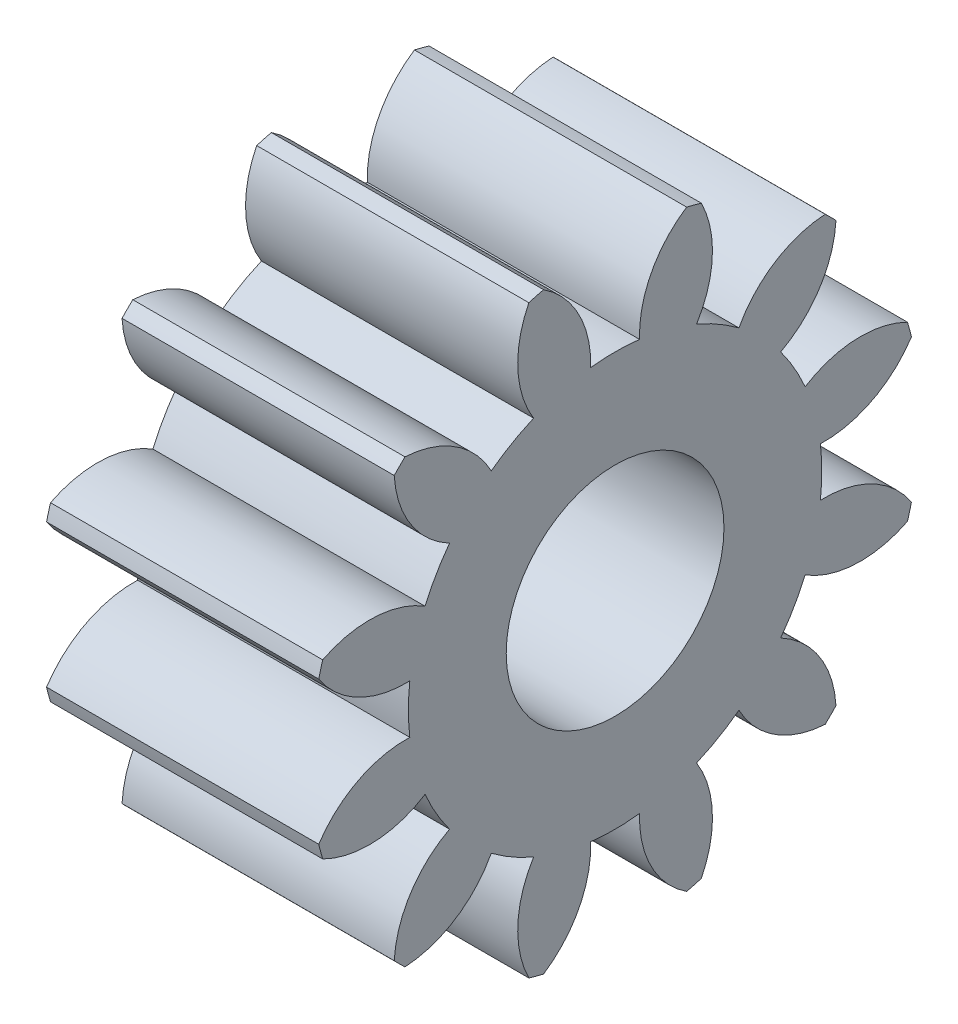
SolidWorks part; units mm, degrees
ref_plane "Plane1" through (0, 0, 0) normal (0, 0, 1) x (1, 0, 0)
ref_plane "Plane2" through (0, 0, 0) normal (0, 1, 0) x (1, 0, 0)
ref_plane "Plane3" through (0, 0, 0) normal (1, 0, 0) x (0, 0, -1)
sketch "HoldingSke" plane through (0, 0, 0) normal (0, 1, 0) x (1, 0, 0)
  line L0 (0, 0) -> (2.4454, -0.5198)
  line L1 (-15, 0) -> (100, 0) construction
  line L2 (0, 0) -> (-2.1039, 2.3779)
  line L3 (0, 0) -> (-11.863, 4.5341)
  line L4 (0, 0) -> (8.4473, 1.7955)
  line L5 (0, 0) -> (-46.8476, -17.4728)
  line L6 (0, 0) -> (-2.0724, -1.3983)
  line L7 (-2.1039, 2.3779) -> (8.6586, 51.2059)
  line L8 (-76.2, 54.61) -> (-75.9, 54.61)
  line L9 (-71.009, 38.7566) -> (-53.1078, 45.2721)
  line L10 (-76.2, 71.12) -> (104.1128, 71.12)
  line L11 (0, 0) -> (-2.5, 0)
  line L12 (-76.2, 101.6) -> (-76.185, 101.6)
  line L13 (24.9733, 27.94) -> (52.9518, 28.4284)
  line L14 (24.9733, 27.94) -> (24.9743, 27.94)
  line L15 (24.9733, 27.94) -> (100.4006, 29.5858)
  line L16 (-63.627, -0.4) -> (-12.827, -0.4)
  circle A0 centre (0, 0) radius 1
  circle A1 centre (0, 0) radius 1.899
  circle A2 centre (0, 0) radius 37.5
  circle A3 centre (0, 0) radius 1
  dimension "Num_teeth" = 12
  dimension "Pitch_radius" = 180.3128
  dimension "Width" = 2.5
  dimension "Thickness" = 2.5
sketch "BasProSke" plane through (0, 0, 0) normal (0, 1, 0) x (1, 0, 0)
  line L0 (-10, 0) -> (60, 0) construction
  line L1 (0, 0) -> (0, 2.8)
  line L2 (0, 0) -> (2.5, 0)
  line L3 (2.5, 0) -> (2.5, 2.8)
  line L4 (2.5, 2.8) -> (0, 2.8)
  dimension "Thickness" = 2.5
  dimension "Diameter" = 5.6
revolve "Base-Revolve" add sketch "BasProSke" angle 360 about L0
sketch "TooCutSke" plane through (0, 0, 0) normal (1, 0, 0) x (0, 0, -1)
  line L1 (0, 0) -> (0, 107) construction
  line L2 (0, 0) -> (-0.3395, 2.3759) construction
  line L3 (0, 0) -> (-1.2334, 4.6032) construction
  line L4 (-0.3395, 2.3759) -> (-0.6167, 2.3016) construction
  arc A0 (0.2246, 1.8857) -> (-0.2246, 1.8857) centre (0, 0) ccw
  arc A1 (0.6868, 2.7407) -> (-0.6868, 2.7407) centre (0, 0) ccw
  circle A2 centre (0, 0) radius 2.4 construction
  circle A3 centre (0, 0) radius 2.2553 construction
  arc A4 (-0.2246, 1.8857) -> (-0.6868, 2.7407) centre (-1.184, 1.9194) ccw
  arc A5 (0.6868, 2.7407) -> (0.2246, 1.8857) centre (1.184, 1.9194) ccw
extrude "ToothCut" cut sketch "TooCutSke" along normal through all
fillet "Breaks" [suppressed] radius 0.008 tangent propagation no
fillet "RootFillets" [suppressed] radius 0.101
pattern_circular "TeethCuts" count 12 every 30 about axis through (-10, 0, 0) along (1, 0, 0) of "ToothCut", "RootFillets", "Breaks"
sketch "HubNeaOneSke" plane through (0, 0, 0) normal (-1, 0, 0) x (0, 0, 1)
  circle A0 centre (0, 0) radius 1.899
  dimension "Diameter" = 3.798
extrude "HubNearOne" [suppressed] add sketch "HubNeaOneSke" along normal blind 47.5001
sketch "HubNeaBotSke" plane through (0, 0, 0) normal (-1, 0, 0) x (0, 0, 1)
  circle A0 centre (0, 0) radius 1.899
  dimension "Diameter" = 3.798
extrude "HubNearBoth" [suppressed] add sketch "HubNeaBotSke" along normal blind 23.75
ref_plane "FarPln" through (2.5, 0, 0) normal (1, 0, 0) x (0, 0, -1)
sketch "HubFarSke" plane through (2.5, 0, 0) normal (1, 0, 0) x (0, 0, -1)
  circle A0 centre (0, 0) radius 1.899
  dimension "Diameter" = 3.798
extrude "HubFar" [suppressed] add sketch "HubFarSke" along normal blind 23.75
sketch "BorSke" plane through (0, 0, 0) normal (1, 0, 0) x (0, 0, -1)
  circle A0 centre (0, 0) radius 1
  dimension "Diameter" = 2
extrude "Bore" cut sketch "BorSke" along normal mid plane 100.0001
sketch "KeySke" plane through (0, 0, 0) normal (1, 0, 0) x (0, 0, -1)
  line L0 (-0.4, 0) -> (-0.4, 1.3)
  line L1 (-0.4, 1.3) -> (0.4, 1.3)
  line L2 (0.4, 1.3) -> (0.4, 0)
  line L3 (0, 0) -> (0, 34) construction
  line L4 (-0.4, 0) -> (0.4, 0)
  dimension "Width" = 0.8
extrude "Keyway" [suppressed] cut sketch "KeySke" along normal mid plane 100.0001
pattern_circular "Keyway2" [suppressed] count 2 every 90 about axis through (-10, 0, 0) along (1, 0, 0) reverse direction yes
equation "' \"Module@HoldingSke\" = 6.35"
equation "' \"Num_teeth@HoldingSke\" = 12"
equation "' \"Ap@HoldingSke\" =  20"
equation "' \"Ap@HoldingSke\" = 20"
equation "' \"Width@HoldingSke\" = 0.5 * 25.4"
equation "' \"Hub_dia@HoldingSke\"= 1 * 25.4"
equation "' \"Hub_dia@HoldingSke\" = 1 * 25.4"
equation "' \"Overall_len@HoldingSke\" = 1.0 * 25.4"
equation "' \"Bore@HoldingSke\" = 0.75 * 25.4"
equation "' \"T_dim@HoldingSke\" = 0.1 * 25.4"
equation "' \"Width@KeySke\" = 0.25 * 25.4"
equation "' \"Show_teeth@HoldingSke\" = 13"
equation "' \"Backlash@HoldingSke\" = 0.009 * 25.4"
equation "' \"Addendum_fac@HoldingSke\" = 1.0"
equation "' \"Dedendum_fac@HoldingSke\" = 1.25"
equation "' \"Dedendum_add@HoldingSke\" = 0.00005 * 25.4"
equation "' \"Clearance_fac@HoldingSke\" = 0.25"
equation "\"Pitch@HoldingSke\" = 1 / \"Module@HoldingSke\""
equation "\"Overcut_dia@TooCutSke\" = (\"Num_teeth@HoldingSke\" + 2 * \"Addendum_fac@HoldingSke\") / \"Pitch@HoldingSke\" + 0.002 * 25.4"
equation "\"Pitch_dia@TooCutSke\" = \"Num_teeth@HoldingSke\" / \"Pitch@HoldingSke\""
equation "\"Base_dia@TooCutSke\" = \"Num_teeth@HoldingSke\" / \"Pitch@HoldingSke\" * cos((\"Ap@HoldingSke\"  * 3.14159265 / 180))"
equation "\"Root_dia@TooCutSke\" = (\"Num_teeth@HoldingSke\" + 2) / \"Pitch@HoldingSke\" - 2 * (\"Addendum_fac@HoldingSke\" + \"Dedendum_fac@HoldingSke\") / \"Pitch@HoldingSke\" - \"Dedendum_add@HoldingSke\" * 2"
equation "\"Half_ang@TooCutSke\" = 180 / \"Num_teeth@HoldingSke\""
equation "\"Half_CT@TooCutSke\" = \"Num_teeth@HoldingSke\" / \"Pitch@HoldingSke\" * sin((3.14159265 / 2 / \"Num_teeth@HoldingSke\")) / 2 - 7 * \"Backlash@HoldingSke\" / 4"
equation "\"Flank_rad@TooCutSke\" = \"Num_teeth@HoldingSke\" / \"Pitch@HoldingSke\" / 5"
equation "\"Radius@RootFillets\" = \"Clearance_fac@HoldingSke\" / \"Pitch@HoldingSke\" + \"Dedendum_add@HoldingSke\""
equation "\"Break_rad@Breaks\" = 0.02 / \"Pitch@HoldingSke\""
equation "\"Thickness@HoldingSke\" = \"Width@HoldingSke\""
equation "\"OAL@HoldingSke\" = \"Thickness@HoldingSke\""
equation "\"MHD@HoldingSke\" = (\"Num_teeth@HoldingSke\" + 2) / \"Pitch@HoldingSke\" - 2 * (\"Addendum_fac@HoldingSke\" + \"Dedendum_fac@HoldingSke\")  / \"Pitch@HoldingSke\" - \"Dedendum_add@HoldingSke\" * 2"
equation "\"MBD@HoldingSke\" = (\"Num_teeth@HoldingSke\" + 2) / \"Pitch@HoldingSke\" - 2 * (\"Addendum_fac@HoldingSke\" + \"Dedendum_fac@HoldingSke\")  / \"Pitch@HoldingSke\" - \"Dedendum_add@HoldingSke\" * 2 - 0.002 * 25.4"
equation "\"MHD@HoldingSke\" = ((sgn( \"MHD@HoldingSke\" - \"Hub_dia@HoldingSke\" )-1)*( \"MHD@HoldingSke\" - \"Hub_dia@HoldingSke\" ))/-2+ \"Hub_dia@HoldingSke\""
equation "\"MBD@HoldingSke\" = ((sgn( \"MBD@HoldingSke\" - \"Bore@HoldingSke\" )-1)*( \"MBD@HoldingSke\" - \"Bore@HoldingSke\" ))/-2+ \"Bore@HoldingSke\""
equation "\"OAL@HoldingSke\" = ((sgn( \"OAL@HoldingSke\" - \"Overall_len@HoldingSke\" )+1)*( \"OAL@HoldingSke\" - \"Overall_len@HoldingSke\" ))/2 + \"Overall_len@HoldingSke\" + 0.000002 * 25.4"
equation "\"Num_teeth@TeethCuts\" = int( \"Show_teeth@HoldingSke\" ) + 1"
equation "\"Num_teeth@TeethCuts\" = ((sgn( \"Num_teeth@TeethCuts\" - \"Num_teeth@HoldingSke\" )-1)*( \"Num_teeth@TeethCuts\" - \"Num_teeth@HoldingSke\" ))/-2+ \"Num_teeth@HoldingSke\""
equation "\"Num_teeth@TeethCuts\" = ((sgn( \"Num_teeth@TeethCuts\" - 2.0)+1)*( \"Num_teeth@TeethCuts\" - 2.0))/2 +2.0"
equation "\"Angle@TeethCuts\" = 360.0 / \"Num_teeth@HoldingSke\""
equation "\"Diameter@BasProSke\" = (\"Num_teeth@HoldingSke\" + 2 * \"Addendum_fac@HoldingSke\") / \"Pitch@HoldingSke\""
equation "\"Thickness@BasProSke\"  = \"Thickness@HoldingSke\""
equation "' \"Fillet_rad@BasProSke\" =  \"Thickness@HoldingSke\" * 0.05"
equation "' \"Fillet_rad@BasProSke\" = \"Thickness@HoldingSke\" * 0.05"
equation "\"MHD@HoldingSke\" = ((sgn( \"MHD@HoldingSke\" - \"Root_dia@TooCutSke\" )-1)*( \"MHD@HoldingSke\" - \"Root_dia@TooCutSke\" ))/-2+ \"Root_dia@TooCutSke\""
equation "\"Diameter@HubNeaOneSke\" = \"MHD@HoldingSke\""
equation "\"Length@HubNearOne\" = \"OAL@HoldingSke\" - \"Thickness@BasProSke\""
equation "\"Diameter@HubNeaBotSke\" = \"MHD@HoldingSke\""
equation "\"Length@HubNearBoth\" = ( \"OAL@HoldingSke\" - \"Thickness@BasProSke\" ) / 2.0"
equation "\"Thickness@FarPln\" = \"Thickness@BasProSke\""
equation "\"Diameter@HubFarSke\" = \"MHD@HoldingSke\""
equation "\"Length@HubFar\" = ( \"OAL@HoldingSke\" - \"Thickness@BasProSke\" ) / 2.0"
equation "\"Diameter@BorSke\" = \"MBD@HoldingSke\""
equation "\"D1@Bore\" = \"OAL@HoldingSke\" * 2.0"
equation "\"D1@Keyway\" = \"OAL@HoldingSke\" * 2.0"
equation "\"Offset@KeySke\" = \"T_dim@HoldingSke\" + \"MBD@HoldingSke\" / 2.0"
